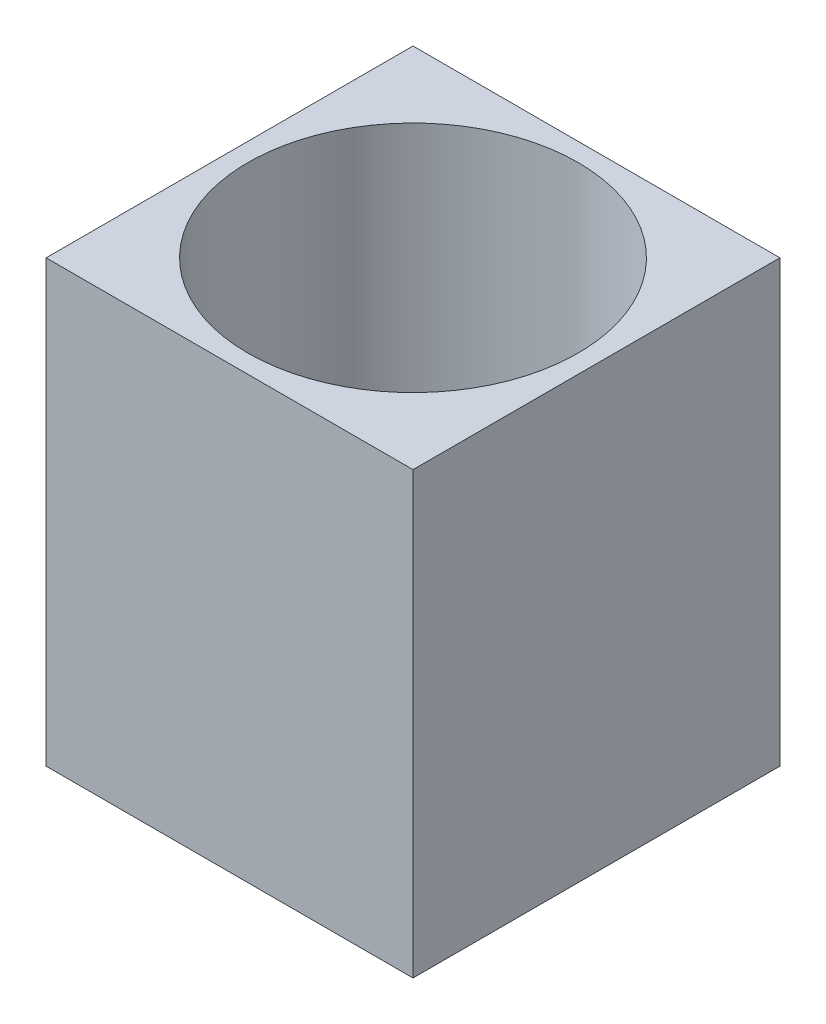
SolidWorks part; units mm, degrees
ref_plane "Front Plane" through (0, 0, 0) normal (0, 0, 1) x (1, 0, 0)
ref_plane "Top Plane" through (0, 0, 0) normal (0, 1, 0) x (1, 0, 0)
ref_plane "Right Plane" through (0, 0, 0) normal (1, 0, 0) x (0, 0, -1)
sketch "Sketch1" plane through (0, 0, 0) normal (0, 1, 0) x (1, 0, 0)
  line L1 (-317.5, -317.5) -> (317.5, -317.5)
  line L2 (-317.5, -317.5) -> (-317.5, 317.5)
  line L3 (-317.5, 317.5) -> (317.5, 317.5)
  line L4 (317.5, -317.5) -> (317.5, 317.5)
  circle A1 centre (0, 0) radius 285.75
  dimension "D4" = 571.5
  dimension "D2" = 635
  dimension "D3" = 635
extrude "Boss-Extrude1" add sketch "Sketch1" along normal blind 508 and the other way blind 254
ref_axis "Axis1" through (-349.25, 0, 0) along (1, 0, 0)
